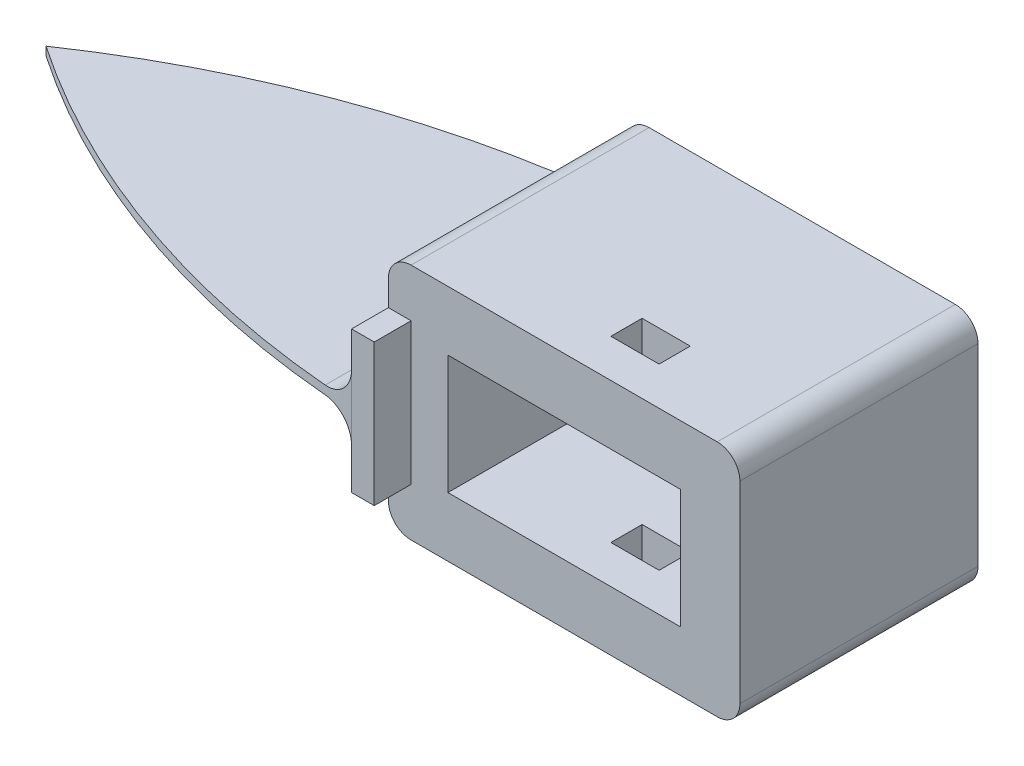
SolidWorks part; units mm, degrees
ref_plane "前基準面" through (0, 0, 0) normal (0, 0, 1) x (1, 0, 0)
ref_plane "上基準面" through (0, 0, 0) normal (0, 1, 0) x (1, 0, 0)
ref_plane "右基準面" through (0, 0, 0) normal (1, 0, 0) x (0, 0, -1)
sketch "Sketch1" plane through (0, 0, 0) normal (0, 0, 1) x (1, 0, 0)
  line L0 (-29.0958, -4.1361) -> (32.9042, -4.1361) construction
  line L1 (-18.5958, 6.3639) -> (22.4042, 6.3639)
  line L2 (-18.5958, 6.3639) -> (-18.5958, -14.6361)
  line L3 (-18.5958, -14.6361) -> (22.4042, -14.6361)
  line L4 (22.4042, 6.3639) -> (22.4042, -14.6361)
  line L5 (-29.0958, 16.8639) -> (32.9042, 16.8639)
  line L6 (-29.0958, 16.8639) -> (-29.0958, -25.1361)
  line L7 (-29.0958, -25.1361) -> (32.9042, -25.1361)
  line L8 (32.9042, 16.8639) -> (32.9042, -25.1361)
  line L9 (1.9042, 16.8639) -> (1.9042, -25.1361) construction
  line L10 (22.4042, -4.1361) -> (-18.5958, -4.1361) construction
  line L11 (1.9042, 6.3639) -> (1.9042, -14.6361) construction
  point P16 (1.9042, -4.1361)
  point P17 (1.9042, -4.1361)
  dimension "D1" = 21
  dimension "D2" = 41
  dimension "D3" = 62
  dimension "D4" = 42
extrude "Boss-Extrude1" add sketch "Sketch1" along normal blind 42
sketch "Sketch2" plane through (0, 0, 42) normal (0, 0, 1) x (1, 0, 0)
  line L0 (-18.5958, -4.1361) -> (-29.0958, -4.1361) construction
  line L1 (-25.0958, -4.1361) -> (-29.0958, -4.1361) construction
  line L3 (-29.0958, 16.8639) -> (-29.0958, -25.1361) construction
  line L4 (-18.5958, 6.3639) -> (-18.5958, -14.6361) construction
  line L5 (-29.0958, 8.3639) -> (-25.0958, 8.3639)
  line L6 (-29.0958, 8.3639) -> (-29.0958, -16.6361)
  line L7 (-29.0958, -16.6361) -> (-25.0958, -16.6361)
  line L8 (-25.0958, 8.3639) -> (-25.0958, -16.6361)
  dimension "D1" = 25
  dimension "D2" = 4
extrude "Boss-Extrude2" add sketch "Sketch2" along normal blind 4.5
extrude "Boss-Extrude3" add sketch "Sketch2<2>" against normal blind 45.55
sketch "Sketch2<2>" plane through (0, 0, 42) normal (0, 0, 1) x (1, 0, 0) same geometry as "Sketch2"
sketch "Sketch3" plane through (0, 0, 46.5) normal (0, 0, 1) x (1, 0, 0)
  line L0 (-60.5958, 2.9639) -> (-59.5958, 2.9639) construction
  line L1 (-25.0958, 8.3639) -> (-60.0958, 8.3639)
  line L2 (-25.0958, 8.3639) -> (-25.0958, -16.6361)
  line L3 (-25.0958, -16.6361) -> (-60.0958, -16.6361)
  line L4 (-60.0958, 8.3639) -> (-60.0958, -16.6361)
  line L5 (-60.5958, 4.4639) -> (-59.5958, 4.4639)
  line L6 (-60.5958, 1.4639) -> (-59.5958, 1.4639)
  line L7 (-60.0958, 8.3639) -> (-60.0958, -16.6361) construction
  line L8 (-60.5559, -11.6762) -> (-59.6357, -11.6762) construction
  line L9 (-60.5559, -10.1762) -> (-59.6357, -10.1762)
  line L10 (-60.5559, -13.1762) -> (-59.6357, -13.1762)
  line L11 (-60.0958, -4.1361) -> (-72.5958, -4.1361) construction
  line L12 (-67.1958, -3.6361) -> (-67.1958, -4.6361) construction
  line L15 (-65.6958, -3.6361) -> (-65.6958, -4.6361)
  line L16 (-68.6958, -3.6361) -> (-68.6958, -4.6361)
  line L17 (-52.9958, -3.6361) -> (-52.9958, -4.6361) construction
  line L18 (-51.4958, -3.6361) -> (-51.4958, -4.6361)
  line L19 (-54.4958, -3.6361) -> (-54.4958, -4.6361)
  line L20 (-60.0958, -4.1361) -> (-25.0958, -4.1361) construction
  line L21 (-29.0958, 8.3639) -> (-29.0958, -16.6361) construction
  arc A0 (-60.0958, 8.3639) -> (-60.0958, -16.6361) centre (-60.0958, -4.1361) ccw
  circle A1 centre (-60.0958, -4.1361) radius 4.05
  arc A3 (-60.5958, 4.4639) -> (-60.5958, 1.4639) centre (-60.5958, 2.9639) ccw
  arc A4 (-59.5958, 1.4639) -> (-59.5958, 4.4639) centre (-59.5958, 2.9639) ccw
  arc A5 (-60.5559, -10.1762) -> (-60.5559, -13.1762) centre (-60.5559, -11.6762) ccw
  arc A6 (-59.6357, -13.1762) -> (-59.6357, -10.1762) centre (-59.6357, -11.6762) ccw
  arc A9 (-65.6958, -3.6361) -> (-68.6958, -3.6361) centre (-67.1958, -3.6361) ccw
  arc A10 (-68.6958, -4.6361) -> (-65.6958, -4.6361) centre (-67.1958, -4.6361) ccw
  arc A11 (-51.4958, -3.6361) -> (-54.4958, -3.6361) centre (-52.9958, -3.6361) ccw
  arc A12 (-54.4958, -4.6361) -> (-51.4958, -4.6361) centre (-52.9958, -4.6361) ccw
  point P9 (-60.0958, 2.9639)
  point P14 (-58.0958, 2.9639)
  point P15 (-62.0958, 2.9639)
  point P19 (-60.0958, -11.6762)
  point P25 (-67.1958, -4.1361)
  point P31 (-67.1958, -2.1361)
  point P32 (-67.1958, -6.1361)
  point P34 (-65.6958, -4.1361)
  point P37 (-52.9958, -4.1361)
  point P42 (-52.9958, -2.1361)
  point P43 (-52.9958, -6.1361)
  line M15 (-29.0958, 8.3639) -> (-29.0958, -16.6361)
  line M16 (-29.0958, -16.6361) -> (-25.0958, -16.6361)
  line M17 (-25.0958, -16.6361) -> (-25.0958, 8.3639)
  line M18 (-25.0958, 8.3639) -> (-29.0958, 8.3639)
  dimension "D2" = 4
  dimension "D10" = 5.6
  dimension "D9" = 4
  dimension "D3" = 3
  dimension "D4" = 5.6
  dimension "D5" = 25
  dimension "D6" = 6.0402
  dimension "D7" = 0
  dimension "D8" = 3
  dimension "D11" = 5.6
  dimension "D12" = 3
  dimension "D13" = 4
  dimension "D14" = 31
extrude "Boss-Extrude6" add sketch "Sketch3" along normal blind 2 contours A5 L9 L4 A1 L6 A3 L5 A0 L10 A10 L16 A9 L15 | A6 L10 L4 L3 L1 L5 A4 L6 A1 L9 A12 L19 A11 L18 M15 | M18 M15 M16 M17 region at (-27.0958, -4.1361, 46.5) region at (-43.7932, -4.1343, 46.5) region at (-60.3753, 6.4139, 46.5)
extrude "Boss-Extrude7" add sketch "Sketch3<8>" against normal blind 53 contours A5 L9 L4 A1 L6 A3 L5 A0 L10 A10 L16 A9 L15 | A6 L10 L4 L3 L1 L5 A4 L6 A1 L9 A12 L19 A11 L18 M15 | M18 M15 M16 M17 region at (-27.0958, -4.1361, 46.5) region at (-43.7932, -4.1343, 46.5) region at (-60.3753, 6.4139, 46.5)
sketch "Sketch3<8>" plane through (0, 0, 46.5) normal (0, 0, 1) x (1, 0, 0) same geometry as "Sketch3"
extrude "Cut-Extrude1" cut sketch "Sketch3<11>" against normal blind 51 contours A6 L10 L4 L3 L1 L5 A4 L6 A1 L9 A12 L19 A11 L18 M15 | A5 L9 L4 A1 L6 A3 L5 A0 L10 A10 L16 A9 L15 region at (-43.7932, -4.1343, 46.5) region at (-60.3753, 6.4139, 46.5)
sketch "Sketch3<11>" plane through (0, 0, 46.5) normal (0, 0, 1) x (1, 0, 0) same geometry as "Sketch3"
sketch "草圖1" plane through (0, 16.8639, 0) normal (0, 1, 0) x (1, 0, 0)
  line L1 (11.9042, -35.25) -> (3.4042, -35.25)
  line L2 (11.9042, -35.25) -> (11.9042, -29.75)
  line L3 (11.9042, -29.75) -> (3.4042, -29.75)
  line L4 (3.4042, -35.25) -> (3.4042, -29.75)
  line L5 (32.9042, -42) -> (-29.0958, -42) construction
  line L7 (22.4042, -42) -> (22.4042, 0) construction
  dimension "D1" = 8.5
  dimension "D2" = 5.5
  dimension "D3" = 10.5
  dimension "D4" = 6.75
extrude "除料-伸長1" cut sketch "草圖1" against normal blind 42
fillet "圓角3" radius 4 1 edges at (-29.0958, 16.8639, 21) type face fillet first side face at (7.6542, 16.8639, 32.5) second side face at (-29.0958, -4.1361, 21)
fillet "圓角4" radius 4 1 edges at (32.9042, 16.8639, 21) type face fillet first side face at (7.6542, 16.8639, 32.5) second side face at (32.9042, -4.1361, 21)
fillet "圓角5" radius 4 1 edges at (32.9042, -25.1361, 21) type face fillet first side face at (7.6542, -25.1361, 32.5) second side face at (32.9042, -6.1361, 21)
fillet "圓角6" radius 4 1 edges at (-29.0958, -25.1361, 21) type face fillet first side face at (7.6542, -25.1361, 32.5) second side face at (-29.0958, -4.8027, 21)
sketch "Sketch8" plane through (0, 0, -6.5) normal (0, 0, -1) x (-1, 0, 0)
  line L0 (29.0958, 8.3639) -> (72.6806, 8.3639)
  line L1 (72.6806, 8.3639) -> (72.6806, -16.7421)
  line L2 (72.6806, -16.7421) -> (29.0958, -16.6361)
  line L3 (29.0958, -16.6361) -> (29.0958, 8.3639)
extrude "Cut-Extrude3" cut sketch "Sketch8" against normal blind 55
sketch "Sketch9" plane through (0, 16.8639, 0) normal (0, 1, 0) x (1, 0, 0)
  line L0 (-29.0958, 6.5) -> (-29.0958, -48.5)
  line L1 (-29.0958, -21) -> (-110.4942, -21)
  arc A0 (-29.0958, 6.5) -> (-110.4942, -21) centre (-20.464, -153.267) ccw
  arc A1 (-110.4942, -21) -> (-29.0958, -48.5) centre (-20.464, 111.267) ccw
extrude "Boss-Extrude8" add sketch "Sketch9" against normal blind 21.25 contours L0 A0 L1 | L1 A1 L0 region at (-59.5483, 16.8639, 10.2538) region at (-59.5483, 16.8639, 31.7462)
extrude "Cut-Extrude4" cut sketch "Sketch9<4>" against normal blind 19.75 contours L0 A0 L1 | L1 A1 L0 region at (-59.5483, 16.8639, 10.2538) region at (-59.5483, 16.8639, 31.7462)
sketch "Sketch9<4>" plane through (0, 16.8639, 0) normal (0, 1, 0) x (1, 0, 0) same geometry as "Sketch9"
fillet "Fillet2" radius 5 1 edges at (-29.0958, -4.3861, 21) type face fillet first side face at (-57.4822, -4.3861, 21) second side face at (-29.0958, -14.6986, 21)
fillet "Fillet3" radius 5 1 edges at (-29.0958, -2.8861, 21) type face fillet first side face at (-29.0958, 6.6764, 21) second side face at (-57.4822, -2.8861, 21)
